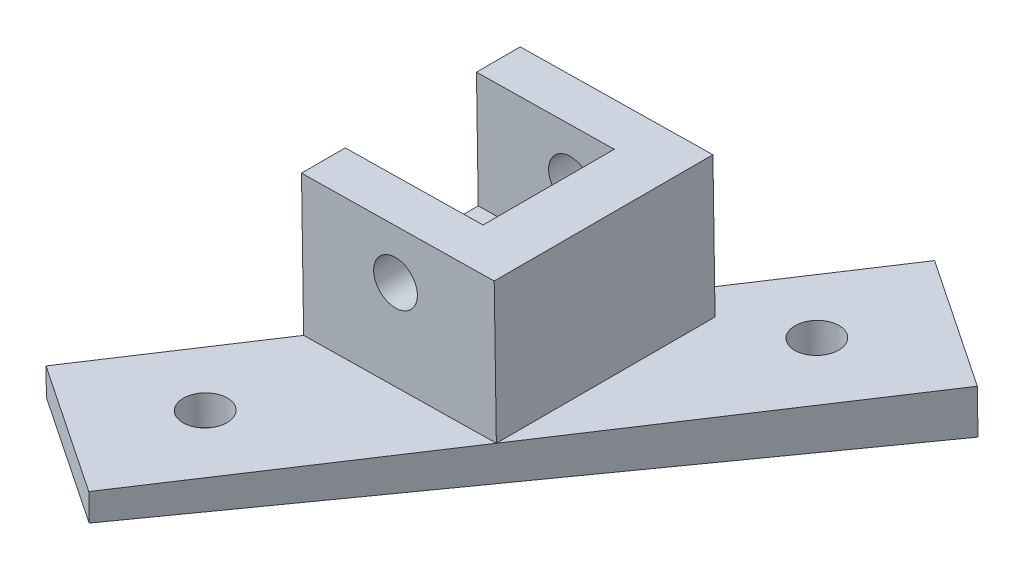
SolidWorks part; units mm, degrees
ref_plane "Front Plane" through (0, 0, 0) normal (0, 0, 1) x (1, 0, 0)
ref_plane "Top Plane" through (0, 0, 0) normal (0, 1, 0) x (1, 0, 0)
ref_plane "Right Plane" through (0, 0, 0) normal (1, 0, 0) x (0, 0, -1)
sketch "Sketch1" plane through (0, 0, 0) normal (0, 0, 1) x (1, 0, 0)
  line L0 (614.2482, 110.6197) -> (642.2246, 111.0468)
  line L1 (604.7125, 110.4741) -> (634.2525, 110.9251) construction
  line L2 (642.2246, 111.0468) -> (642.5336, 90.8054)
  line L3 (642.5336, 90.8054) -> (614.5573, 90.3783)
  line L4 (614.5573, 90.3783) -> (614.2482, 110.6197)
  line L5 (606.4491, 93.8109) -> (629.5989, 94.1643) construction
  line L6 (522.1487, 25.7254) -> (633.9027, 25.7254) construction
  line L7 (522.1487, 25.7254) -> (633.9027, 25.7254)
  line L8 (614.5573, 87.1817) -> (642.5336, 87.1817)
  line L9 (642.5336, 87.1817) -> (642.5336, 90.8054)
  line L10 (614.5573, 87.1817) -> (614.5573, 90.3783)
  line L15 (634.4712, 96.6012) -> (604.3912, 96.1419)
  line L16 (606.4491, 93.8109) -> (629.5989, 94.1643)
  line L18 (634.4712, 96.6012) -> (604.3912, 96.1419)
  line L19 (606.4491, 93.8109) -> (629.5989, 94.1643)
  arc A0 (634.4712, 96.6012) -> (634.2525, 110.9251) centre (627.8931, 103.6644) ccw construction
  arc A1 (634.2525, 110.9251) -> (634.4712, 96.6012) centre (627.8931, 103.6644) cw
  arc A3 (629.5989, 94.1643) -> (634.4712, 96.6012) centre (627.8931, 103.6644) ccw
  arc A4 (629.5989, 94.1643) -> (634.4712, 96.6012) centre (627.8931, 103.6644) ccw
  spline S2 degree 3 poles (2552.9367, 546.0286) (733.5016, 155.6074) (601.1661, 109.3829) (604.4885, 95.4418) (604.5493, 95.2808) (604.6964, 94.9846) (604.783, 94.8489) (604.9677, 94.606) (605.0672, 94.4967) (605.3783, 94.2032) (605.5939, 94.059) (618.5563, 88.1204) (617.8976, 247.6862) (-411.651, 1813.6619) knots -9.933415 -9.933415 -9.933415 -9.933415 0.125 0.125 0.25 0.25 0.375 0.375 0.5 0.5 0.75 0.75 15.365298 15.365298 15.365298 15.365298 only from (604.3912, 96.1419) to (606.4491, 93.8109)
  spline S4 degree 3 poles (604.3912, 96.1419) (604.3871, 95.9602) (604.4069, 95.7841) (604.4885, 95.4418) (604.5493, 95.2808) (604.6964, 94.9846) (604.783, 94.8489) (604.9677, 94.606) (605.0672, 94.4967) (605.3783, 94.2032) (605.5939, 94.059) (606.0299, 93.8592) (606.244, 93.8078) (606.4491, 93.8109) knots 0 0 0 0 0.125 0.125 0.25 0.25 0.375 0.375 0.5 0.5 0.75 0.75 1 1 1 1
  dimension "D2" = 14.4425
  dimension "D1" = 3.556
  dimension "D3" = 0
extrude "Boss-Extrude2" add sketch "Sketch1" against normal up to surface (19.05 mm away) contours L19 L4 L3 L2 L0 A1 A4 region at (638.2439, 110.6378, 0)
sketch "Sketch2" plane through (0, 0, 0) normal (0, 0, 1) x (1, 0, 0)
  line L0 (614.5573, 90.3783) -> (614.2482, 110.6197)
  line L1 (604.7125, 110.4741) -> (634.2525, 110.9251) construction
  line L2 (614.2482, 110.6197) -> (642.2246, 111.0468)
  line L3 (642.2246, 111.0468) -> (642.5336, 90.8054)
  line L4 (642.5336, 90.8054) -> (614.5573, 90.3783)
extrude "Boss-Extrude3" add sketch "Sketch2" along normal blind 6.35 contours L4 L0 L2 L3
sketch "Sketch4" plane through (0, 0, -19.05) normal (0, 0, -1) x (-1, 0, 0)
  line L0 (-614.5573, 90.3783) -> (-614.2482, 110.6197)
  line L1 (-604.6203, 110.4727) -> (-634.2525, 110.9251) construction
  line L2 (-614.2482, 110.6197) -> (-642.2246, 111.0468)
  line L3 (-642.2246, 111.0468) -> (-642.5336, 90.8054)
  line L4 (-642.5336, 90.8054) -> (-614.5573, 90.3783)
extrude "Boss-Extrude4" add sketch "Sketch4" along normal blind 6.35
sketch "Sketch5" plane through (0, 0, 0) normal (0, 0, -1) x (-1, 0, 0)
  circle A0 centre (-627.8931, 103.6644) radius 3.175
extrude "Cut-Extrude1" cut sketch "Sketch5" against normal through all
sketch "Sketch6" plane through (0, 0, -19.05) normal (0, 0, 1) x (1, 0, 0)
  circle A0 centre (627.8931, 103.6644) radius 3.175
extrude "Cut-Extrude2" cut sketch "Sketch6" against normal through all
sketch "Sketch9" plane through (0, 0, 6.35) normal (0, 0, 1) x (1, 0, 0)
  line L2 (522.1487, 25.7254) -> (633.9027, 25.7254) construction
  line L3 (522.1487, 25.7254) -> (633.9027, 25.7254)
  line L6 (614.5573, 90.3783) -> (642.5336, 90.8054)
  line L7 (614.5573, 80.0701) -> (642.5898, 80.0701)
  line L8 (642.5898, 80.0701) -> (642.5336, 90.8054)
  line L9 (614.5573, 80.0701) -> (614.5573, 90.3783)
sketch "Sketch11" plane through (-1.2363, 80.9766, 0) normal (0.0153, -0.9999, 0) x (0.9999, 0.0153, 0)
  line L0 (615.8653, 6.35) -> (600.7721, 28.6587)
  line L1 (600.7721, 28.6587) -> (619.966, 41.6445)
  line L2 (619.966, 41.6445) -> (643.845, 6.35)
  line L3 (643.845, -25.4) -> (643.845, 6.35) construction
  line L4 (643.845, 6.35) -> (615.8653, 6.35) construction
  line L5 (643.845, 6.35) -> (672.0232, -35.299)
  line L6 (672.0232, -35.299) -> (652.8293, -48.2849)
  line L7 (652.8293, -48.2849) -> (615.8653, 6.35)
  dimension "D1" = 124.081
  dimension "D2" = 90
extrude "Boss-Extrude7" add sketch "Sketch11" along normal blind 7.874
sketch "Sketch12" plane through (-1.2363, 80.9766, 0) normal (-0.0153, 0.9999, 0) x (0.9999, 0.0153, 0)
  line L0 (643.845, -6.35) -> (619.966, -41.6445) construction
  line L1 (672.0232, 35.299) -> (643.845, -6.35) construction
  line L2 (619.966, -41.6445) -> (600.7721, -28.6587) construction
  line L3 (652.8293, 48.2849) -> (672.0232, 35.299) construction
  circle A0 centre (618.1913, -22.9636) radius 3.175
  circle A1 centre (654.0226, 29.9972) radius 3.175
  dimension "D1" = 11.938
  dimension "D2" = 11.938
  dimension "D3" = 14.478
  dimension "D4" = 14.478
extrude "Cut-Extrude4" cut sketch "Sketch12" against normal through all
sketch "Sketch13" plane through (444.5691, 6.7875, 300.8145) normal (0.8282, 0.0126, 0.5604) x (0.5603, 0.0086, -0.8282)
  line L0 (312.9136, 73.112) -> (312.9136, 73.0669)
  line L1 (312.9136, 73.0669) -> (405.7053, 70.6587)
  line L2 (405.7053, 70.6587) -> (405.8128, 73.112)
  line L3 (405.8128, 73.112) -> (312.9136, 73.112)
  line L5 (138.8906, 16.5856) -> (339.6635, 11.3751) construction
  line L6 (138.8906, 16.5856) -> (339.6635, 11.3751)
  line M9 (312.9136, 73.112) -> (405.8128, 73.112)
extrude "Boss-Extrude8" add sketch "Sketch13" against normal blind 23.1648 contours L1 L2 L0 M9 region at (653.1576, 82.2745, -9.1585)
sketch "Sketch14" plane through (444.5691, 6.7875, 300.8145) normal (0.8282, 0.0126, 0.5604) x (0.5603, 0.0086, -0.8282)
  line L0 (312.9136, 73.0669) -> (312.9136, 77.0455)
  line L1 (312.9136, 73.0669) -> (312.9136, 80.986) construction
  line L2 (312.9136, 77.0455) -> (405.8128, 74.6374)
  line L3 (405.8128, 73.112) -> (405.8128, 80.986) construction
  line L4 (405.8128, 74.6374) -> (405.7053, 70.6587)
  line L5 (405.7053, 70.6587) -> (312.9136, 73.0669)
  dimension "D1" = 3.9787
  dimension "D2" = 3.9787
extrude "Cut-Extrude6" cut sketch "Sketch14" against normal through all
